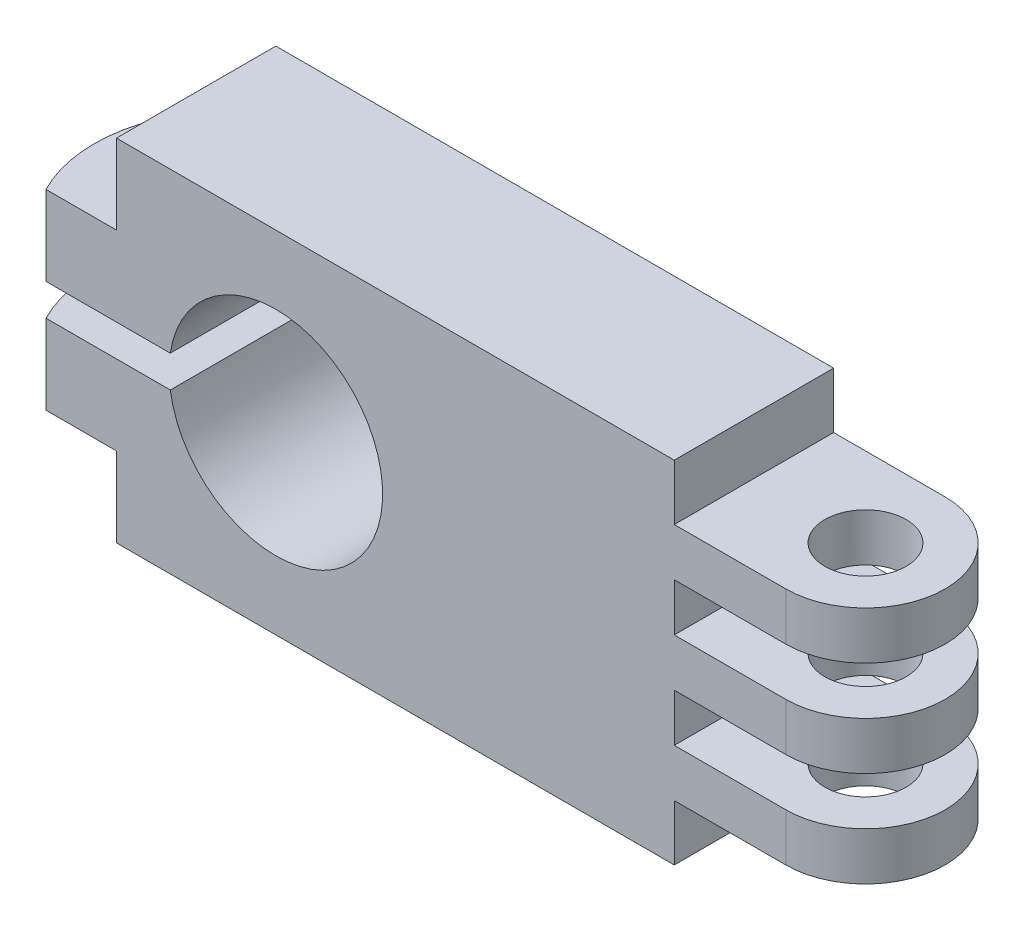
SolidWorks part; units mm, degrees
ref_plane "前视基准面" through (0, 0, 0) normal (0, 0, 1) x (1, 0, 0)
ref_plane "上视基准面" through (0, 0, 0) normal (0, 1, 0) x (1, 0, 0)
ref_plane "右视基准面" through (0, 0, 0) normal (1, 0, 0) x (0, 0, -1)
sketch "草图1" plane through (0, 0, 0) normal (0, 0, 1) x (1, 0, 0)
  line L0 (0, 0) -> (35, 0)
  line L1 (35, 0) -> (35, -3.5)
  line L2 (35, -3.5) -> (47, -3.5)
  line L3 (47, -3.5) -> (47, -6.5)
  line L4 (47, -6.5) -> (35, -6.5)
  line L5 (35, -6.5) -> (35, -9.5)
  line L6 (35, -9.5) -> (47, -9.5)
  line L7 (47, -9.5) -> (47, -12.5)
  line L8 (47, -12.5) -> (35, -12.5)
  line L9 (35, -12.5) -> (35, -15.5)
  line L10 (35, -15.5) -> (47, -15.5)
  line L11 (47, -15.5) -> (47, -18.5)
  line L12 (47, -18.5) -> (35, -18.5)
  line L13 (35, -18.5) -> (35, -22)
  line L14 (35, -22) -> (0, -22)
  line L15 (0, -22) -> (0, -17)
  line L16 (0, -17) -> (-10, -17)
  line L17 (-10, -17) -> (-10, -12)
  line L21 (-10, -10) -> (0, -10)
  line L22 (-10, -10) -> (-10, -5)
  line L26 (0, -10) -> (0, -12)
  line L27 (0, -12) -> (-10, -12)
  line L28 (-10, -5) -> (0, -5)
  line L29 (0, -5) -> (0, 0)
extrude "凸台-拉伸1" add sketch "草图1" along normal blind 10 contours L29 L0 L1 L2 L3 L4 L5 L6 L7 L8 L9 L10 L11 L12 L13 L14 L15 L16 L17 L27 L26 L21 L22 L28
sketch "草图2" plane through (0, -3.5, 0) normal (0, 1, 0) x (1, 0, 0)
  line L0 (47, -5) -> (42, -5) construction
  line L1 (47, -10) -> (47, 0) construction
  circle A0 centre (42, -5) radius 2.55
extrude "切除-拉伸1" cut sketch "草图2" against normal blind 19
sketch "草图3" plane through (0, -3.5, 0) normal (0, 1, 0) x (1, 0, 0)
  line L0 (42, 0) -> (35, 0)
  line L1 (35, -10) -> (35, 0) construction
  line L2 (35, 0) -> (35, 1.3629)
  line L3 (35, 1.3629) -> (53.3289, 1.3629)
  line L4 (53.3289, 1.3629) -> (53.3289, -13.8132)
  line L5 (53.3289, -13.8132) -> (35, -13.8132)
  line L6 (35, -13.8132) -> (35, -10)
  line L7 (35, -10) -> (42, -10)
  arc A0 (42, -10) -> (42, 0) centre (42, -5) ccw
extrude "切除-拉伸2" cut sketch "草图3" against normal blind 19
sketch "草图5" plane through (0, 0, 10) normal (0, 0, 1) x (1, 0, 0)
  line L0 (0, -11) -> (10, -11) construction
  line L1 (0, -10) -> (0, -12) construction
  line L3 (0, -10) -> (10, -10)
  line L4 (0, -10) -> (0, -12)
  line L5 (0, -12) -> (10, -12)
  line L6 (10, -10) -> (10, -12)
extrude "切除-拉伸4" cut sketch "草图5" against normal blind 19
sketch "草图6" plane through (0, 0, 10) normal (0, 0, 1) x (1, 0, 0)
  line L0 (10, -12) -> (10, -10) construction
  circle A0 centre (10, -11) radius 6.7
extrude "切除-拉伸5" cut sketch "草图6" against normal blind 19
sketch "草图7" plane through (0, -5, 0) normal (0, 1, 0) x (1, 0, 0)
  line L0 (-10, 0) -> (0, 0) construction
  line L1 (-10, -10) -> (0, -10) construction
  line L2 (-4.4228, -10) -> (-4.4228, -16.2455)
  line L3 (-4.4228, -16.2455) -> (-15.2417, -16.2455)
  line L4 (-15.2417, -16.2455) -> (-15.2417, 3.3262)
  line L5 (-15.2417, 3.3262) -> (-3, 3.3262)
  line L6 (-3, 3.3262) -> (-3, 0)
  arc A0 (-3, 0) -> (-4.4228, -10) centre (3.3167, -6) ccw
extrude "切除-拉伸6" cut sketch "草图7" against normal blind 19
sketch "草图8" plane through (0, -5, 0) normal (0, 1, 0) x (1, 0, 0)
  circle A1 centre (-2.5, -6) radius 1
  point P0 (0, 0)
extrude "切除-拉伸7" cut sketch "草图8" against normal blind 18
